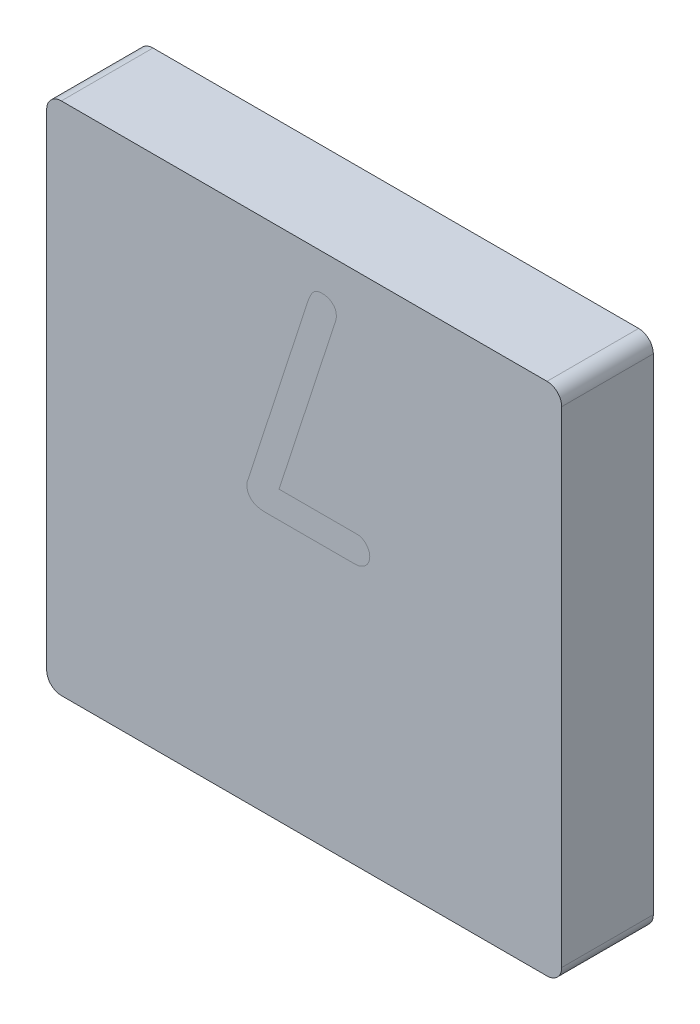
SolidWorks part; units mm, degrees
material "Nylon 101"
ref_plane "Front Plane" through (0, 0, 0) normal (0, 0, 1) x (1, 0, 0)
ref_plane "Top Plane" through (0, 0, 0) normal (0, 1, 0) x (1, 0, 0)
ref_plane "Right Plane" through (0, 0, 0) normal (1, 0, 0) x (0, 0, -1)
sketch "Sketch1" plane through (0, 0, 0) normal (0, 0, 1) x (1, 0, 0)
  line L0 (4.207, 4.715) -> (-4.207, 4.715) construction
  line L1 (4.715, -4.207) -> (4.715, 4.207) construction
  line L2 (-4.207, -4.715) -> (4.207, -4.715) construction
  line L3 (-4.715, 4.207) -> (-4.715, -4.207) construction
  line L4 (4.207, 4.715) -> (-4.207, 4.715) construction
  line L5 (4.715, -4.207) -> (4.715, 4.207) construction
  line L6 (-4.207, -4.715) -> (4.207, -4.715) construction
  line L7 (-4.715, 4.207) -> (-4.715, -4.207) construction
  line L8 (4.207, 4.461) -> (-4.207, 4.461)
  line L9 (-4.461, 4.207) -> (-4.461, -4.207)
  line L10 (-4.207, -4.461) -> (4.207, -4.461)
  line L11 (4.461, -4.207) -> (4.461, 4.207)
  arc A0 (4.715, 4.207) -> (4.207, 4.715) centre (4.207, 4.207) ccw construction
  arc A1 (4.207, -4.715) -> (4.715, -4.207) centre (4.207, -4.207) ccw construction
  arc A2 (-4.715, -4.207) -> (-4.207, -4.715) centre (-4.207, -4.207) ccw construction
  arc A3 (-4.207, 4.715) -> (-4.715, 4.207) centre (-4.207, 4.207) ccw construction
  arc A4 (4.715, 4.207) -> (4.207, 4.715) centre (4.207, 4.207) ccw construction
  arc A5 (4.207, -4.715) -> (4.715, -4.207) centre (4.207, -4.207) ccw construction
  arc A6 (-4.715, -4.207) -> (-4.207, -4.715) centre (-4.207, -4.207) ccw construction
  arc A7 (-4.207, 4.715) -> (-4.715, 4.207) centre (-4.207, 4.207) ccw construction
  arc A8 (-4.207, 4.461) -> (-4.461, 4.207) centre (-4.207, 4.207) ccw
  arc A9 (-4.461, -4.207) -> (-4.207, -4.461) centre (-4.207, -4.207) ccw
  arc A10 (4.207, -4.461) -> (4.461, -4.207) centre (4.207, -4.207) ccw
  arc A11 (4.461, 4.207) -> (4.207, 4.461) centre (4.207, 4.207) ccw
  dimension "D1" = 0.254
extrude "Boss-Extrude1" add sketch "Sketch1" along normal blind 1.5875
sketch "Sketch2" plane through (0, 0, 1.5875) normal (0, 0, 1) x (1, 0, 0)
  line L0 (4.461, 3.8355) -> (-4.461, 3.8355) construction
  line L1 (4.461, -4.207) -> (4.461, 4.207) construction
  line L2 (-4.461, 4.207) -> (-4.461, -4.207) construction
  text T0 "7" font "GordonURWMed" height in points 16
sketch "Sketch4" plane through (0, 0, 1.5875) normal (0, 0, 1) x (1, 0, 0)
  line L0 (4.461, -0.7785) -> (-4.461, -0.7785) construction
  line L1 (4.461, -4.207) -> (4.461, 4.207) construction
  line L2 (-4.461, 4.207) -> (-4.461, -4.207) construction
  text T0 "N" font "GordonURWMed" height in points 12
wrap "Direction" [suppressed] sketch "Sketch4" source sketch "Sketch4"
split line "Number"
sketch "Sketch5" [suppressed] plane through (0, 0, 1.5875) normal (0, 0, 1) x (1, 0, 0)
  line L0 (4.461, 0) -> (-4.461, 0) construction
  line L1 (4.461, -4.207) -> (4.461, 4.207) construction
  line L2 (-4.461, 4.207) -> (-4.461, -4.207) construction
  line L3 (4.461, 1.651) -> (-4.461, 1.651) construction
  text T0 "CLR" font "GordonURWMed" height in points 14
  dimension "D1" = 1.651
wrap "CLR" [suppressed] sketch "Sketch5" source sketch "Sketch5"
sketch "Sketch6" [suppressed] plane through (0, 0, 1.5875) normal (0, 0, 1) x (1, 0, 0)
  line L0 (4.461, 0) -> (-4.461, 0) construction
  line L4 (4.461, 1.651) -> (-4.461, 1.651) construction
  text T0 "ENT" font "GordonURWCon" height in points 16
  dimension "D1" = 1.651
wrap "ENT" [suppressed] sketch "Sketch6" source sketch "Sketch6"
sketch "Sketch8" [suppressed] plane through (0, 0, 1.5875) normal (0, 0, 1) x (1, 0, 0)
  line L0 (4.461, 3.302) -> (-4.461, 3.302) construction
  line L3 (4.461, 0) -> (-4.461, 0) construction
  line L4 (4.461, -0.508) -> (-4.461, -0.508) construction
  text T0 "EM" font "GordonURWCon" height in points 14
  text T1 "CON" font "GordonURWCon" height in points 14
  point P13 (0, 0)
  dimension "D1" = 3.302
  dimension "D2" = 0.508
wrap "EMCON" [suppressed] sketch "Sketch8" source sketch "Sketch8"
sketch "Sketch9" [suppressed] plane through (0, 0, 0) normal (0, 0, 1) x (1, 0, 0)
  line L0 (4.461, 3.302) -> (-4.461, 3.302) construction
  line L3 (4.461, 0) -> (-4.461, 0) construction
  line L4 (4.461, -0.508) -> (-4.461, -0.508) construction
  text T0 "ON" font "GordonURWCon" height in points 14
  text T1 "OFF" font "GordonURWCon" height in points 14
  point P13 (0, 0)
  dimension "D1" = 3.302
  dimension "D2" = 0.508
wrap "ON-OFF" [suppressed] sketch "Sketch9" source sketch "Sketch9" thickness 0.0762 parameters "D1"=0.0762
sketch "Sketch10" [suppressed] plane through (0, 0, 0) normal (0, 0, 1) x (1, 0, 0)
  line L0 (4.461, 0) -> (-4.461, 0) construction
  line L4 (4.461, 1.651) -> (-4.461, 1.651) construction
  text T0 "IFF" font "GordonURWCon" height in points 16
  dimension "D1" = 1.651
wrap "LEGEND" [suppressed] sketch "Sketch10" source sketch "Sketch10" thickness 0.0762 parameters "D1"=0.0762
